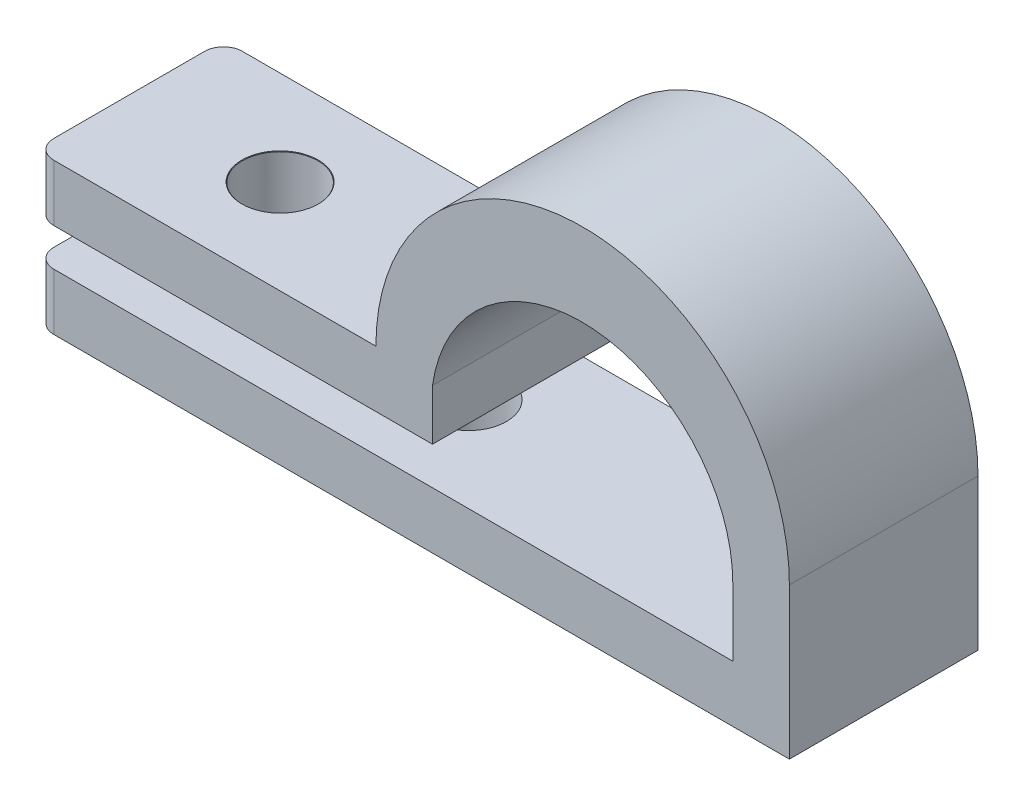
SolidWorks part; units mm, degrees
ref_plane "Front Plane" through (0, 0, 0) normal (0, 0, 1) x (1, 0, 0)
ref_plane "Top Plane" through (0, 0, 0) normal (0, 1, 0) x (1, 0, 0)
ref_plane "Right Plane" through (0, 0, 0) normal (1, 0, 0) x (0, 0, -1)
sketch "Sketch1" plane through (0, 0, 0) normal (0, 0, 1) x (1, 0, 0)
  line L0 (-23.9266, 0) -> (89.2302, 0) construction
  line L1 (0, -20.5085) -> (0, 45.1548) construction
  line L2 (0, 0) -> (40, 0)
  line L3 (0, 0) -> (0, 3)
  line L4 (0, 3) -> (37, 3)
  line L5 (0, 5) -> (21.0791, 5)
  line L6 (0, 5) -> (0, 8)
  line L7 (0, 8) -> (18.0791, 8)
  line L8 (40, -14.1781) -> (40, 14.7215) construction
  line L9 (37, -5.7871) -> (37, 20.3577) construction
  line L10 (18.0791, -5.23) -> (18.0791, 20.0532) construction
  line L11 (21.0791, -3.9975) -> (21.0791, 25.2141) construction
  line L12 (37, 3) -> (37, 6.5734)
  line L13 (40, 0) -> (40, 8)
  line L14 (21.0791, 5) -> (21.0791, 7.6955)
  arc A2 (40, 8) -> (18.0791, 8) centre (29.0395, 8) ccw
  arc A4 (21.0791, 7.6955) -> (37, 6.5734) centre (29, 6.5734) cw
  dimension "D3" = 3
  dimension "D5" = 8
  dimension "D1" = 40
  dimension "D2" = 3
  dimension "D4" = 2
  dimension "D6" = 3
  dimension "D7" = 3
extrude "Boss-Extrude1" add sketch "Sketch1" along normal blind 5 and the other way blind 5
fillet "Fillet1" radius 1 4 edges at (0, 1.5, 5) (0, 6.5, 5) (0, 1.5, -5) (0, 6.5, -5)
sketch "Sketch3" plane through (0, 8, 0) normal (0, 1, 0) x (1, 0, 0)
  line L0 (-6.1699, 0) -> (30.8303, 0) construction
  line L1 (0, -9.5724) -> (0, 9.7319) construction
  point P4 (8, 0)
  point P6 (18, 0)
  dimension "D1" = 8
  dimension "D2" = 10
hole_wizard "Ø4.0mm Dowel Hole1" positions "Sketch4" profile "Sketch5" hole size "Ø4.0" standard "ANSI Metric" end condition through all
sketch "Sketch4" plane through (0, 8, 0) normal (0, 1, 0) x (1, 0, 0)
  point P0 (8, 0)
  point P3 (18, 0)
sketch "Sketch5" plane through (8, 8, 0) normal (1, 0, 0) x (0, 0, 1)
  line L0 (0, 0) -> (0, 8)
  line L1 (0, 8) -> (2, 8)
  line L2 (2, 8) -> (2, 0.025)
  line L3 (2, 0.025) -> (2.025, 0)
  line L5 (2.025, 0) -> (0, 0)
  line L6 (-2, 0.025) -> (-2.025, 0) construction
  line L11 (0, -6.35) -> (0, 107.95) construction
  dimension "Thru Hole Dia." = 4
  dimension "Thru Hole Depth" = 8
  dimension "Near C'Sink Dia." = 4.05
  dimension "Near C'Sink Angle" = 90
